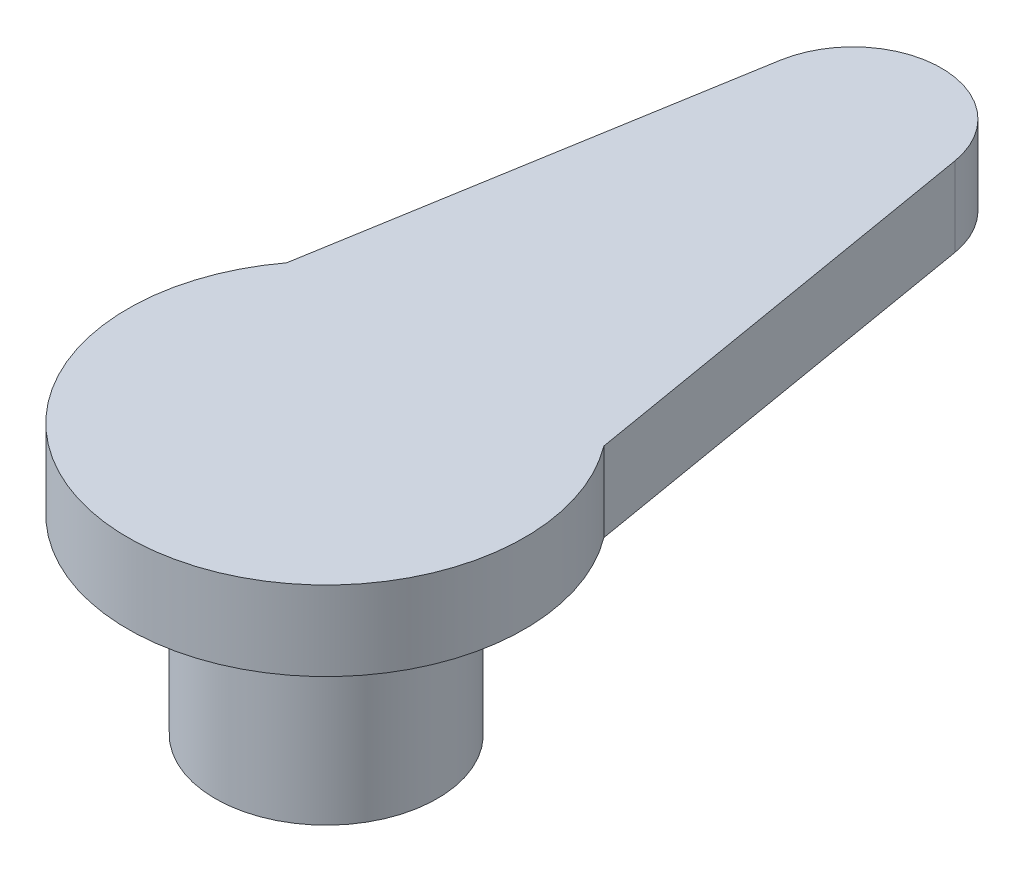
SolidWorks part; units mm, degrees
ref_plane "Front Plane" through (0, 0, 0) normal (0, 0, 1) x (1, 0, 0)
ref_plane "Top Plane" through (0, 0, 0) normal (0, 1, 0) x (1, 0, 0)
ref_plane "Right Plane" through (0, 0, 0) normal (1, 0, 0) x (0, 0, -1)
sketch "Sketch1" plane through (0, 0, 0) normal (0, 1, 0) x (1, 0, 0)
  line L0 (5, 3.75) -> (2.75, 17.0612)
  line L1 (-5, 3.75) -> (-2.75, 17.0612)
  circle A0 centre (0, 0) radius 6.25
  arc A1 (-2.75, 17.0612) -> (2.75, 17.0612) centre (0, 16.5963) cw
  dimension "D1" = 12.5
  dimension "D2" = 10
  dimension "D3" = 5.5
  dimension "D4" = 13.5
extrude "Boss-Extrude1" add sketch "Sketch1" along normal blind 2.5 contours A1 L1 A0 L0 | A0 region at (0, 0, -11.513) region at (0, 0, 0)
sketch "Sketch2" plane through (0, 0, 0) normal (0, -1, 0) x (1, 0, 0)
  circle A0 centre (0, 0) radius 3.5
  dimension "D1" = 7
extrude "Boss-Extrude2" add sketch "Sketch2" along normal blind 6
sketch "Sketch3" plane through (0, -6, 0) normal (0, -1, 0) x (1, 0, 0)
  line L0 (1.4595, -1.475) -> (-1.4595, -1.475)
  circle A0 centre (0, 0) radius 2.075
  point P5 (0, 2.075)
  dimension "D1" = 4.15
  dimension "D2" = 3.55
extrude "Cut-Extrude1" cut sketch "Sketch3" against normal up to surface (6 mm away) contours L0 A0 region at (0, -6, 0.1682) up to face at (0, 0, 3.5)
